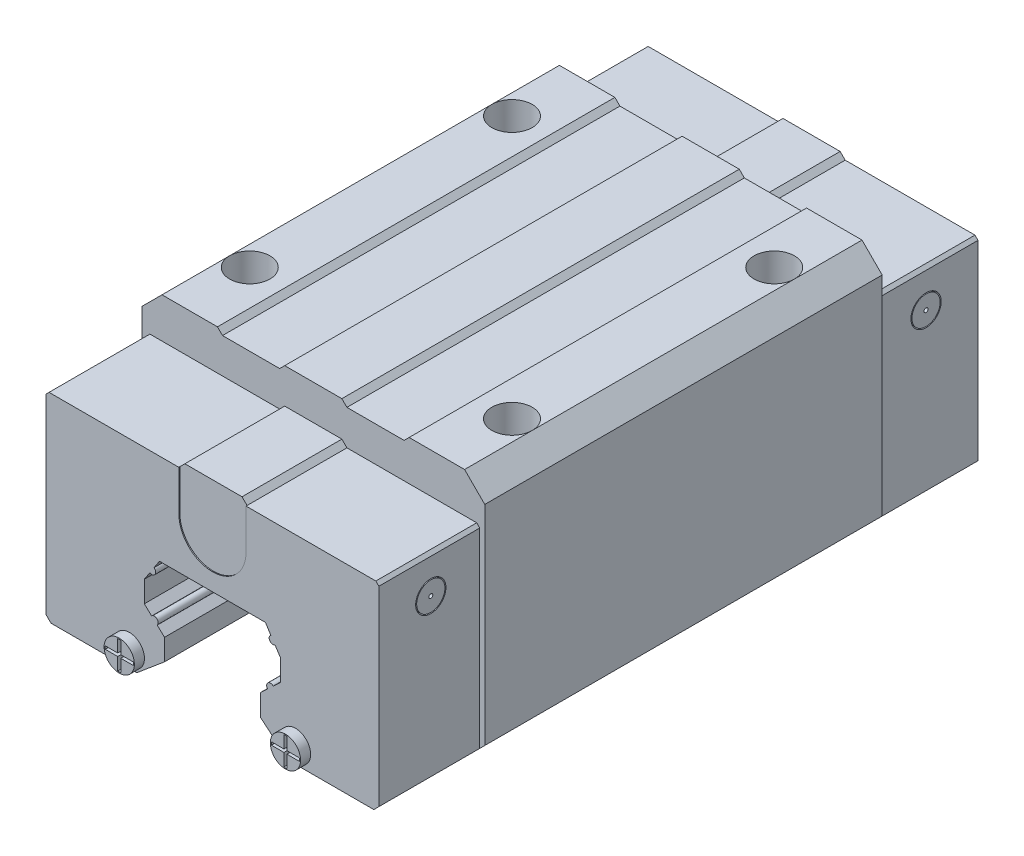
SolidWorks part; units mm, degrees
ref_plane "前视基准面" through (0, 0, 0) normal (0, 0, 1) x (1, 0, 0)
ref_plane "上视基准面" through (0, 0, 0) normal (0, 1, 0) x (1, 0, 0)
ref_plane "右视基准面" through (0, 0, 0) normal (1, 0, 0) x (0, 0, -1)
sketch "基准草图" plane through (0, 0, 0) normal (1, 0, 0) x (0, 0, -1)
  line L0 (0, 0) -> (60, 0) construction
  line L1 (0, 0) -> (0, 5)
  line L2 (60, 0) -> (80, 0) construction
  dimension "数量" = 5
  dimension "P" = 60
  dimension "E" = 20
sketch "草图1" plane through (0, 0, 0) normal (0, 0, 1) x (1, 0, 0)
  line L0 (0, 23.7) -> (0, 0) construction
  line L1 (-17, 21.7) -> (-17, 17.7)
  line L2 (17, 21.7) -> (17, 1)
  line L3 (-13, 23.7) -> (-13, 19.725) construction
  line L4 (-9.5, 23.7) -> (-9, 23.2)
  line L5 (-9, 23.2) -> (-3.3333, 23.2)
  line L6 (-3.3333, 23.2) -> (-2.8333, 23.7)
  line L7 (9.5, 23.7) -> (9, 23.2)
  line L8 (9, 23.2) -> (3.3333, 23.2)
  line L9 (3.3333, 23.2) -> (2.8333, 23.7)
  line L10 (-9.5, 23.7) -> (-15, 23.7)
  line L11 (15, 23.7) -> (9.5, 23.7)
  line L12 (-15, 23.7) -> (-17, 21.7)
  line L13 (2.8333, 23.7) -> (-2.8333, 23.7)
  line L14 (-16.2, 19.725) -> (16.2, 19.725)
  line L15 (-16.2, 19.725) -> (-16.5, 19.425)
  line L16 (-16.5, 19.425) -> (-16.5, 0.5)
  line L17 (-17, 17.7) -> (-16.5, 17.2) construction
  line L18 (-3.3333, 19.725) -> (-3.3333, 15.75)
  line L19 (3.3333, 19.725) -> (3.3333, 15.75)
  line L21 (-16, 0) -> (-7.5, 0)
  line L22 (-7.5, 0) -> (-4.75, 2.3075)
  line L23 (15, 23.7) -> (17, 21.7)
  line L24 (-4.75, 2.3075) -> (-4.75, 4.4182)
  line L25 (-4.75, 4.4182) -> (-5.4765, 5.0996)
  line L26 (-6.75, 6.294) -> (-6.75, 8.4047)
  line L27 (-6.75, 8.4047) -> (-6.2051, 9.2384)
  line L28 (-5.25, 10.7) -> (5.25, 10.7)
  line L29 (6.75, 8.4047) -> (6.2051, 9.2384)
  line L30 (6.75, 6.294) -> (6.75, 8.4047)
  line L31 (4.75, 4.4182) -> (5.4765, 5.0996)
  line L32 (4.75, 2.3075) -> (4.75, 4.4182)
  line L33 (7.5, 0) -> (4.75, 2.3075)
  line L34 (16, 0) -> (7.5, 0)
  line L35 (16.5, 19.425) -> (16.5, 0.5)
  line L36 (16.2, 19.725) -> (16.5, 19.425)
  line L37 (-7.5, 0) -> (-7.5, -3.8)
  line L38 (-7.5, -3.8) -> (-7, -4.3)
  line L39 (-7, -4.3) -> (-1.5, -4.3)
  line L40 (7.5, -3.8) -> (7, -4.3)
  line L41 (7.5, 0) -> (7.5, -3.8)
  line L42 (-1.5, -4.3) -> (-1, -3.8)
  line L43 (-1, -3.8) -> (1, -3.8)
  line L44 (1.5, -4.3) -> (1, -3.8)
  line L45 (1.5, -4.3) -> (7, -4.3)
  line L46 (-6.0235, 5.6126) -> (-6.75, 6.294)
  line L47 (-5.7949, 9.8662) -> (-5.25, 10.7)
  line L48 (5.7949, 9.8662) -> (5.25, 10.7)
  line L49 (6.0235, 5.6126) -> (6.75, 6.294)
  line L51 (8.2379, 3.1) -> (8.2379, 0.1) construction
  line L52 (6.7379, 1.6) -> (9.7379, 1.6) construction
  line L53 (8.0879, 2.9919) -> (8.0879, 1.75)
  line L54 (8.0879, 1.75) -> (6.846, 1.75)
  line L55 (8.3879, 1.75) -> (9.6299, 1.75)
  line L56 (8.3879, 2.9919) -> (8.3879, 1.75)
  line L57 (8.0879, 1.45) -> (6.846, 1.45)
  line L58 (8.3879, 1.45) -> (9.6299, 1.45)
  line L59 (8.3879, 0.2081) -> (8.3879, 1.45)
  line L60 (8.0879, 0.2081) -> (8.0879, 1.45)
  line L61 (-8.0879, 1.45) -> (-6.846, 1.45)
  line L62 (-8.0879, 0.2081) -> (-8.0879, 1.45)
  line L63 (-8.3879, 0.2081) -> (-8.3879, 1.45)
  line L64 (-8.3879, 1.45) -> (-9.6299, 1.45)
  line L65 (-8.3879, 1.75) -> (-9.6299, 1.75)
  line L66 (-8.0879, 1.75) -> (-6.846, 1.75)
  line L67 (-8.0879, 2.9919) -> (-8.0879, 1.75)
  line L68 (-8.3879, 2.9919) -> (-8.3879, 1.75)
  line L69 (-2.8333, 20.225) -> (2.8333, 20.225)
  line L70 (-3.3333, 19.725) -> (-2.8333, 20.225)
  line L71 (-16.75, 17.45) -> (-16.75, 0.75)
  line L72 (3.3333, 19.725) -> (2.8333, 20.225)
  line L73 (-16.75, 17.45) -> (-17, 17.7)
  line L74 (-16, 0) -> (-16.75, 0.75)
  line L75 (16, 0) -> (17, 1)
  arc A0 (-3.3333, 15.75) -> (3.3333, 15.75) centre (0, 15.75) ccw
  arc A1 (-6.2051, 9.2384) -> (-5.7949, 9.8662) centre (-6, 9.5523) ccw
  arc A2 (-5.4765, 5.0996) -> (-6.0235, 5.6126) centre (-5.75, 5.3561) ccw
  arc A3 (5.4765, 5.0996) -> (6.0235, 5.6126) centre (5.75, 5.3561) cw
  arc A4 (6.2051, 9.2384) -> (5.7949, 9.8662) centre (6, 9.5523) cw
  circle A5 centre (8.2379, 1.6) radius 1.5
  circle A6 centre (-8.2379, 1.6) radius 1.5
  circle A7 centre (8.2379, 1.6) radius 1.4
  circle A8 centre (-8.2379, 1.6) radius 1.4
  point P4 (-13, 23.7)
  point P6 (13, 23.7)
  point P11 (-9.5, 23.7)
  point P12 (-2.8333, 23.7)
  point P13 (9.5, 23.7)
  point P14 (2.8333, 23.7)
  point P55 (-7.5, 0)
  point P60 (0, 12.4167)
  dimension "D18" = 0.75
  dimension "D19" = 0.75
  dimension "D20" = 3
  dimension "D21" = 1.7
  dimension "D24" = 0.1
  dimension "D25" = 1.6
  dimension "D1" = 2
  dimension "D2" = 45
  dimension "W" = 34
  dimension "D3" = 45
  dimension "B1" = 4
  dimension "B" = 26
  dimension "T" = 6
  dimension "H" = 28
  dimension "D4" = 45
  dimension "D5" = 0.5
  dimension "D6" = 6.6667
  dimension "D7" = 45
  dimension "D8" = 0.5
  dimension "D9" = 0.5
  dimension "H2" = 7.95
  dimension "D10" = 3.975
  dimension "D11" = 45
  dimension "Wr" = 15
  dimension "D12" = 2
  dimension "N" = 9.5
  dimension "D13" = 45
  dimension "D14" = 9.5
  dimension "H1" = 4.3
  dimension "D15" = 0.3
  dimension "D16" = 10.5
  dimension "D17" = 0.3
  dimension "D22" = 0.3
  dimension "D23" = 0.3
  dimension "D26" = 0.5
  dimension "D27" = 45
  dimension "Hr" = 15
  dimension "D28" = 1.5
  dimension "D29" = 100
  dimension "D30" = 40
  dimension "D31" = 1
  dimension "D32" = 1
  dimension "D33" = 45
extrude "凸台-拉伸11" add sketch "草图1" along normal mid plane 59.4 contours A4 L29 L30 L49 A3 L31 L32 L33 L34 L35 L36 L14 L19 A0 L18 L15 L16 L21 L22 L24 L25 A2 L46 L26 L27 A1 L47 L28 L48 A5 A6 | L18 A0 L19 L69 | L14 L72 L69 L70 region at (-16.1155, 9.9625, 0) region at (0, 19.9682, 0) region at (0, 16.3865, 0)
extrude "凸台-拉伸12" add sketch "草图1<12>" along normal mid plane 61.4 contours A5 | A6
sketch "草图1<12>" plane through (0, 0, 0) normal (0, 0, 1) x (1, 0, 0) same geometry as "草图1"
extrude "凸台-拉伸13" add sketch "草图1<13>" along normal mid plane 39.4 contours L2 L23 L11 L7 L8 L9 L13 L6 L5 L4 L10 L12 L1 L17 L16 L15 L14 L36 L35 region at (0.515, 20.4225, 0)
sketch "草图1<13>" plane through (0, 0, 0) normal (0, 0, 1) x (1, 0, 0) same geometry as "草图1"
sketch "草图4" plane through (0, 0, 30.7) normal (0, 0, 1) x (1, 0, 0)
  line L0 (8.0879, 1.75) -> (6.846, 1.75) construction
  line L1 (8.0879, 2.9919) -> (8.0879, 1.75) construction
  line L2 (8.3879, 2.9919) -> (8.3879, 1.75) construction
  line L3 (8.3879, 1.75) -> (9.6299, 1.75) construction
  line L4 (8.3879, 1.45) -> (9.6299, 1.45) construction
  line L5 (8.3879, 0.2081) -> (8.3879, 1.45) construction
  line L6 (8.0879, 0.2081) -> (8.0879, 1.45) construction
  line L7 (8.0879, 1.45) -> (6.846, 1.45) construction
  line L8 (8.0879, 1.75) -> (6.846, 1.75)
  line L9 (8.0879, 2.9919) -> (8.0879, 1.75)
  line L10 (8.3879, 2.9919) -> (8.3879, 1.75)
  line L11 (8.3879, 1.75) -> (9.6299, 1.75)
  line L12 (8.3879, 1.45) -> (9.6299, 1.45)
  line L13 (8.3879, 0.2081) -> (8.3879, 1.45)
  line L14 (8.0879, 0.2081) -> (8.0879, 1.45)
  line L15 (8.0879, 1.45) -> (6.846, 1.45)
  line L16 (-8.0879, 2.9919) -> (-8.0879, 1.75) construction
  line L17 (-8.3879, 2.9919) -> (-8.3879, 1.75) construction
  line L18 (-8.3879, 1.75) -> (-9.6299, 1.75) construction
  line L19 (-8.3879, 1.45) -> (-9.6299, 1.45) construction
  line L20 (-8.3879, 0.2081) -> (-8.3879, 1.45) construction
  line L21 (-8.0879, 0.2081) -> (-8.0879, 1.45) construction
  line L22 (-8.0879, 1.45) -> (-6.846, 1.45) construction
  line L23 (-8.0879, 1.75) -> (-6.846, 1.75) construction
  line L24 (-8.0879, 2.9919) -> (-8.0879, 1.75)
  line L25 (-8.3879, 2.9919) -> (-8.3879, 1.75)
  line L26 (-8.3879, 1.75) -> (-9.6299, 1.75)
  line L27 (-8.3879, 1.45) -> (-9.6299, 1.45)
  line L28 (-8.3879, 0.2081) -> (-8.3879, 1.45)
  line L29 (-8.0879, 0.2081) -> (-8.0879, 1.45)
  line L30 (-8.0879, 1.45) -> (-6.846, 1.45)
  line L31 (-8.0879, 1.75) -> (-6.846, 1.75)
  circle A0 centre (8.2379, 1.6) radius 1.4 construction
  arc A1 (6.846, 1.75) -> (6.846, 1.45) centre (8.2379, 1.6) ccw
  arc A2 (8.0879, 0.2081) -> (8.3879, 0.2081) centre (8.2379, 1.6) ccw
  arc A3 (8.3879, 2.9919) -> (8.0879, 2.9919) centre (8.2379, 1.6) ccw
  arc A4 (9.6299, 1.45) -> (9.6299, 1.75) centre (8.2379, 1.6) ccw
  circle A5 centre (-8.2379, 1.6) radius 1.4 construction
  arc A6 (-9.6299, 1.75) -> (-9.6299, 1.45) centre (-8.2379, 1.6) ccw
  arc A7 (-8.0879, 2.9919) -> (-8.3879, 2.9919) centre (-8.2379, 1.6) ccw
  arc A8 (-6.846, 1.45) -> (-6.846, 1.75) centre (-8.2379, 1.6) ccw
  arc A9 (-8.3879, 0.2081) -> (-8.0879, 0.2081) centre (-8.2379, 1.6) ccw
extrude "切除-拉伸1" cut sketch "草图4" against normal blind 0.5
mirror "镜向1" about plane through (0, 0, 0) normal (0, 0, 1) of "切除-拉伸1"
sketch "草图8" plane through (0, 0, 29.7) normal (0, 0, 1) x (1, 0, 0)
  line L3 (3.3333, 19.725) -> (3.3333, 15.75) construction
  line L4 (-3.3333, 19.725) -> (-3.3333, 15.75) construction
  line L5 (-16.2, 19.725) -> (16.2, 19.725) construction
  line L6 (-3.3333, 19.725) -> (-2.8333, 20.225) construction
  line L7 (-2.8333, 20.225) -> (2.8333, 20.225) construction
  line L8 (3.3333, 19.725) -> (2.8333, 20.225) construction
  line L9 (3.3333, 19.725) -> (3.3333, 15.75)
  line L10 (-3.3333, 19.725) -> (-3.3333, 15.75)
  line L11 (-16.2, 19.725) -> (-3.3333, 19.725)
  line L12 (-3.3333, 19.725) -> (-2.8333, 20.225)
  line L13 (-2.8333, 20.225) -> (2.8333, 20.225)
  line L14 (3.3333, 19.725) -> (2.8333, 20.225)
  line L15 (3.3333, 19.725) -> (16.2, 19.725)
  arc A0 (-3.3333, 15.75) -> (3.3333, 15.75) centre (0, 15.75) ccw construction
  arc A1 (-3.3333, 15.75) -> (3.3333, 15.75) centre (0, 15.75) ccw
  line M2 (2.8333, 20.225) -> (-2.8333, 20.225)
  line M41 (3.3333, 19.725) -> (2.8333, 20.225)
  line M42 (-2.8333, 20.225) -> (-3.3333, 19.725)
extrude "切除-拉伸6" cut sketch "草图8" against normal blind 0.1 contours L10 A1 L9 M41 M2 M42 region at (0, 16.6213, 29.7)
ref_plane "基准面1" through (0, 15.75, 0) normal (0, 1, 0) x (-1, 0, 0)
sketch "草图13" plane through (16.5, 0, 0) normal (1, 0, 0) x (0, 0, -1)
  line L0 (-19.7, 21.7) -> (-19.7, 1) construction
  line L1 (-19.7, 23.7) -> (19.7, 23.7) construction
  line L2 (0, 23.7) -> (0, 0) construction
  circle A0 centre (-24.55, 16) radius 1.5
  circle A1 centre (24.55, 16) radius 1.5
  circle A2 centre (-24.55, 16) radius 1.4
  circle A3 centre (-24.55, 16) radius 0.2
  circle A4 centre (24.55, 16) radius 0.2
  circle A5 centre (24.55, 16) radius 1.4
  dimension "D1" = 3
  dimension "D2" = 2.8
  dimension "D3" = 0.4
  dimension "K2" = 4.85
  dimension "H3" = 7.7
extrude "切除-拉伸9" cut sketch "草图13" against normal blind 5 contours A0 A2 | A3 | A1 A5 | A4 region at (16.5, 16, 26.0076) region at (16.5, 16, -23.0924) region at (16.5, 16, 24.55) region at (16.5, 16, -24.55)
sketch "草图14" plane through (0, 23.7, 0) normal (0, 1, 0) x (1, 0, 0)
  line L0 (-15, 0) -> (15, 0) construction
  line L1 (-15, -19.7) -> (-15, 19.7) construction
  line L2 (15, -19.7) -> (15, 19.7) construction
  line L3 (0, 19.7) -> (0, -19.7) construction
  line L4 (-2.8333, 19.7) -> (2.8333, 19.7) construction
  line L5 (-2.8333, -19.7) -> (2.8333, -19.7) construction
  circle A0 centre (-13, 13) radius 2
  circle A1 centre (13, 13) radius 2
  circle A2 centre (13, -13) radius 2
  circle A3 centre (-13, -13) radius 2
  dimension "D1" = 4
  dimension "D2" = 26
  dimension "D3" = 26
extrude "切除-拉伸10" cut sketch "草图14" against normal blind 5
